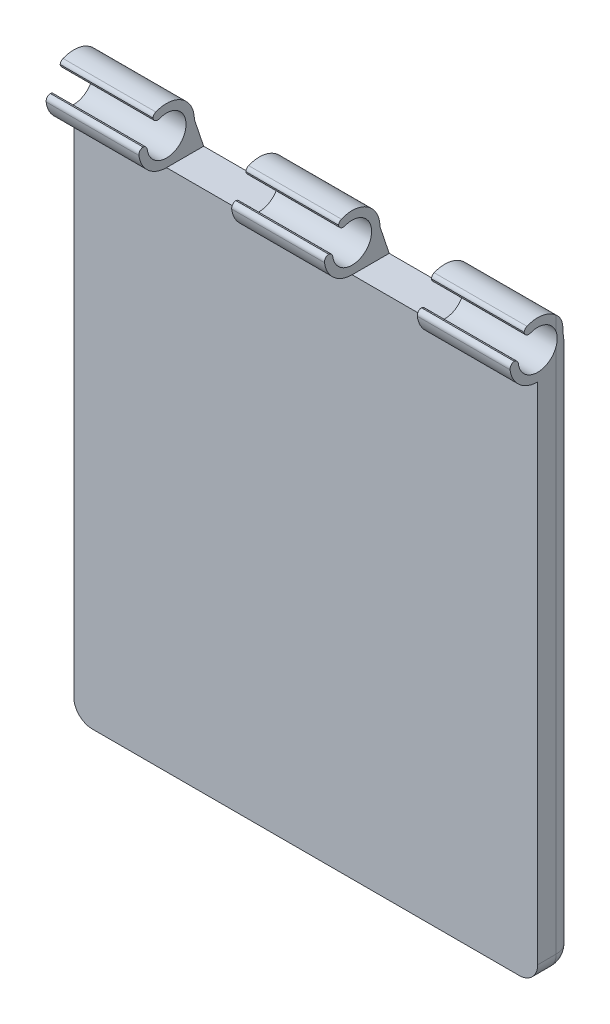
SolidWorks part; units mm, degrees
ref_plane "Front Plane" through (0, 0, 0) normal (0, 0, 1) x (1, 0, 0)
ref_plane "Top Plane" through (0, 0, 0) normal (0, 1, 0) x (1, 0, 0)
ref_plane "Right Plane" through (0, 0, 0) normal (1, 0, 0) x (0, 0, -1)
sketch "Sketch1" plane through (0, 0, 0) normal (0, 0, 1) x (1, 0, 0)
  line L1 (-12.5, -14.1) -> (12.5, -14.1)
  line L2 (-12.5, -14.1) -> (-12.5, 14.1)
  line L3 (-12.5, 14.1) -> (12.5, 14.1)
  line L4 (12.5, -14.1) -> (12.5, 14.1)
  line L5 (-12.5, -14.1) -> (12.5, 14.1) construction
  line L6 (-12.5, 14.1) -> (12.5, -14.1) construction
  point P0 (0, 0)
  dimension "D1" = 25
  dimension "D2" = 28.2
extrude "Boss-Extrude1" add sketch "Sketch1" along normal blind 2
sketch "Sketch5" plane through (-12.5, 0, 0) normal (-1, 0, 0) x (0, 0, 1)
  line L0 (2, 14.1) -> (2, 15.6) construction
  line L1 (0.5, 15.6) -> (0, 14.1)
  line L6 (0, 14.1) -> (0, -14.1)
  line L7 (0, -14.1) -> (2, -14.1)
  line L8 (2, -14.1) -> (2, 14.1)
  line L9 (2, 14.1) -> (0, 14.1)
  line L13 (2, 14.1) -> (0, 14.1)
  arc A0 (2, 14.1) -> (0.5, 15.6) centre (2, 15.6) ccw
  dimension "D1" = 3
  dimension "D2" = 0
extrude "Boss-Extrude2" add sketch "Sketch5" against normal blind 5
pattern_linear "LPattern1" count 3 spacing 10 along (1, 0, 0) of "Boss-Extrude2"
sketch "Sketch6" plane through (-12.5, 0, 0) normal (-1, 0, 0) x (0, 0, 1)
  circle A0 centre (2, 15.6) radius 1.5 construction
  circle A1 centre (2, 15.6) radius 1.05
extrude "Cut-Extrude1" cut sketch "Sketch6" against normal through all
fillet "Fillet1" radius 1 3 edges at (12.5, 0, 0) (0, -14.1, 0) (-12.5, 0, 0)
fillet "Fillet2" radius 1 4 edges at (12.2071, -13.8071, 0.2929) (-12.2071, -13.8071, 0.2929) (12.5, -14.1, 1.5) (-12.5, -14.1, 1.5)
sketch "Sketch7" plane through (-12.5, 0, 0) normal (-1, 0, 0) x (0, 0, 1)
  line L0 (2, 14.1) -> (2, -13.1) construction
  line L1 (2.7336, 16.9083) -> (4.671, 16.9083)
  line L2 (2.7336, 16.9083) -> (2.7336, 15.697)
  line L3 (2.7336, 15.697) -> (4.671, 15.697)
  line L4 (4.671, 16.9083) -> (4.671, 15.697)
  line L5 (1, -13.1) -> (2, -13.1) construction
  arc A0 (2, 14.1) -> (1, 16.718) centre (2, 15.6) ccw construction
  dimension "D1" = 0.7336
  dimension "D2" = 2.671
  dimension "D3" = 28.797
extrude "Cut-Extrude2" cut sketch "Sketch7" against normal through all
fillet "Fillet7" radius 0.254 12 edges at (-10, 15.697, 3.4969) (-10, 15.697, 3.0455) (-10, 16.3512, 2.7336) (-10, 16.9083, 2.7336) (10, 15.697, 3.4969) (10, 15.697, 3.0455) (10, 16.3512, 2.7336) (10, 16.9083, 2.7336) (0, 15.697, 3.4969) (0, 15.697, 3.0455) (0, 16.3512, 2.7336) (0, 16.9083, 2.7336)
